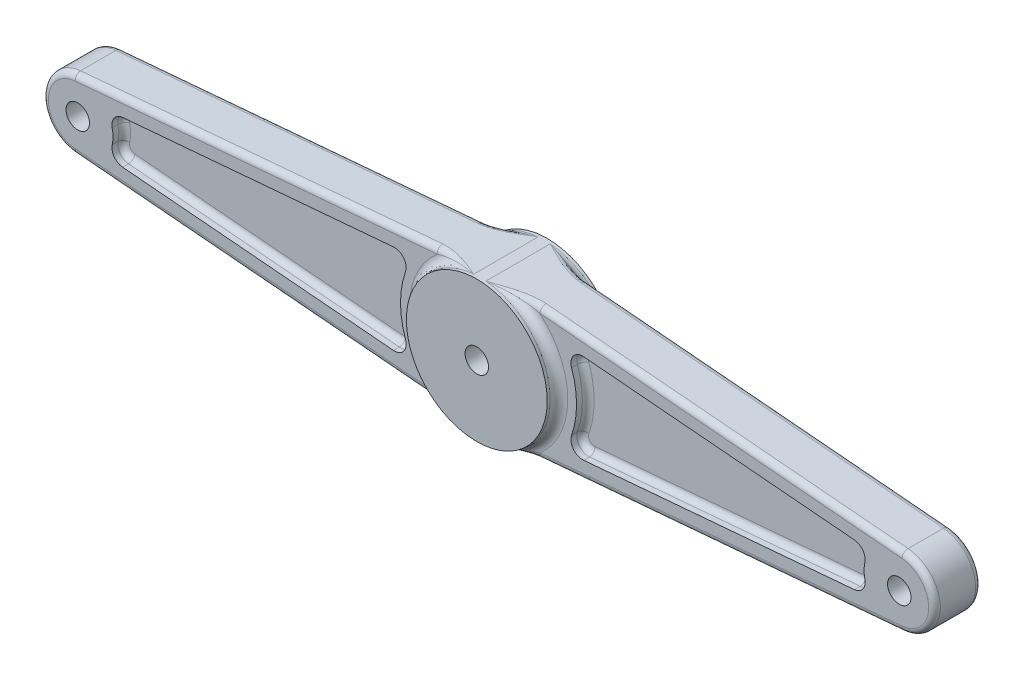
SolidWorks part; units mm, degrees
material "AISI 4340 Steel, annealed"
ref_plane "Front Plane" through (0, 0, 0) normal (0, 0, 1) x (1, 0, 0)
ref_plane "Top Plane" through (0, 0, 0) normal (0, 1, 0) x (1, 0, 0)
ref_plane "Right Plane" through (0, 0, 0) normal (1, 0, 0) x (0, 0, -1)
sketch "Sketch1" plane through (0, 0, 0) normal (0, 0, 1) x (1, 0, 0)
  line L0 (-70.5143, 5.9779) -> (-1.0286, 11.9558)
  line L1 (70.5143, 5.9779) -> (1.0286, 11.9558)
  line L2 (1.0286, -11.9558) -> (70.5143, -5.9779)
  line L3 (-70.5143, -5.9779) -> (-1.0286, -11.9558)
  arc A0 (-1.0286, -11.9558) -> (1.0286, -11.9558) centre (0, 0) ccw
  arc A1 (70.5143, -5.9779) -> (70.5143, 5.9779) centre (70, 0) ccw
  arc A2 (-70.5143, 5.9779) -> (-70.5143, -5.9779) centre (-70, 0) ccw
  arc A3 (1.0286, 11.9558) -> (-1.0286, 11.9558) centre (0, 0) ccw
  circle A4 centre (-70, 0) radius 2
  circle A5 centre (0, 0) radius 2
  circle A6 centre (70, 0) radius 2
  dimension "D1" = 24
  dimension "D2" = 12
  dimension "D3" = 140
  dimension "D5" = 4
  dimension "D4" = 70
extrude "Boss-Extrude1" add sketch "Sketch1" along normal mid plane 8
sketch "Sketch2" plane through (0, 0, 0) normal (0, 0, 1) x (1, 0, 0)
  circle A0 centre (0, 0) radius 12
  dimension "D1" = 24
extrude "Boss-Extrude2" add sketch "Sketch2" along normal mid plane 12
sketch "Sketch3" plane through (0, 0, 4) normal (0, 0, 1) x (1, 0, 0)
  circle A0 centre (0, 0) radius 2
  dimension "D1" = 4
extrude "Cut-Extrude1" cut sketch "Sketch3" against normal mid plane 45
sketch "Sketch4" plane through (0, 0, 4) normal (0, 0, 1) x (1, 0, 0)
  line L0 (16.2063, -7.639) -> (62.3491, -3.6693)
  line L1 (1.0286, -11.9558) -> (70.5143, -5.9779) construction
  line L6 (-62.3491, 3.6693) -> (-16.2063, 7.639)
  line L8 (-62.3491, -3.6693) -> (-16.2063, -7.639)
  line L9 (16.2063, 7.639) -> (62.3491, 3.6693)
  arc A0 (-14.1485, 4.9821) -> (-14.1485, -4.9821) centre (0, 0) ccw
  arc A1 (-64.1333, -1.2575) -> (-64.1333, 1.2575) centre (-70, 0) ccw
  arc A2 (1.0286, -11.9558) -> (1.0286, 11.9558) centre (0, 0) ccw construction
  arc A3 (64.1333, 1.2575) -> (64.1333, -1.2575) centre (70, 0) ccw
  arc A5 (14.1485, -4.9821) -> (14.1485, 4.9821) centre (0, 0) ccw
  arc A6 (64.1333, -1.2575) -> (62.3491, -3.6693) centre (62.1777, -1.6767) cw
  arc A7 (64.1333, 1.2575) -> (62.3491, 3.6693) centre (62.1777, 1.6767) ccw
  arc A8 (16.2063, -7.639) -> (14.1485, -4.9821) centre (16.0349, -5.6464) cw
  arc A9 (16.2063, 7.639) -> (14.1485, 4.9821) centre (16.0349, 5.6464) ccw
  arc A10 (-14.1485, -4.9821) -> (-16.2063, -7.639) centre (-16.0349, -5.6464) cw
  arc A11 (-14.1485, 4.9821) -> (-16.2063, 7.639) centre (-16.0349, 5.6464) ccw
  arc A12 (-62.3491, -3.6693) -> (-64.1333, -1.2575) centre (-62.1777, -1.6767) cw
  arc A13 (-62.3491, 3.6693) -> (-64.1333, 1.2575) centre (-62.1777, 1.6767) ccw
  point P20 (65.0801, 3.4343)
  point P26 (12.7273, 7.9383)
  point P30 (-12.7273, -7.9383)
  point P36 (-12.7273, 7.9383)
  point P39 (-65.0801, -3.4343)
  point P42 (-65.0801, 3.4343)
  dimension "D1" = 3
  dimension "D2" = 6
  dimension "D3" = 12
  dimension "D13" = 2
  dimension "D4" = 3
  dimension "D5" = 5.4342
  dimension "D6" = 57.787
  dimension "D7" = 83.2416
  dimension "D8" = 83.2416
  dimension "D9" = 69.4857
  dimension "D10" = 69.4857
  dimension "D11" = 135.5944
  dimension "D12" = 135.5944
extrude "Cut-Extrude2" cut sketch "Sketch4" against normal blind 2
mirror "Mirror1" about plane through (0, 0, 0) normal (0, 0, 1) of "Cut-Extrude2"
fillet "Fillet1" radius 1 16 edges at (-14.4537, 6.871, 2) (-15, 0, 2) (-14.4537, -6.871, 2) (-39.2777, -5.6541, 2) (-63.7855, -2.8661, 2) (-64, 0, 2) (-63.7855, 2.8661, 2) (14.4537, 6.871, 2) (39.2777, 5.6541, 2) (63.7855, 2.8661, 2) (64, 0, 2) (63.7855, -2.8661, 2) (39.2777, -5.6541, 2) (14.4537, -6.871, 2) (-39.2777, 5.6541, 2) (15, 0, 2)
fillet "Fillet2" radius 1 16 edges at (63.7855, 2.8661, -2) (64, 0, -2) (63.7855, -2.8661, -2) (39.2777, -5.6541, -2) (14.4537, -6.871, -2) (15, 0, -2) (14.4537, 6.871, -2) (-14.4537, -6.871, -2) (-39.2777, -5.6541, -2) (-63.7855, -2.8661, -2) (-64, 0, -2) (-63.7855, 2.8661, -2) (-39.2777, 5.6541, -2) (-14.4537, 6.871, -2) (39.2777, 5.6541, -2) (-15, 0, -2)
fillet "Fillet3" radius 1.5 4 edges at (12, 0, 4) (-12, 0, 4) (-12, 0, -4) (12, 0, -4)
fillet "Fillet4" radius 1 20 edges at (-4.2015, 11.6829, 4.4638) (-38.8524, 8.7018, 4) (-76, 0, 4) (-4.2015, -11.6829, 4.4638) (4.2015, -11.6829, 4.4638) (38.8524, -8.7018, 4) (76, 0, 4) (4.2015, 11.6829, 4.4638) (-4.2015, 11.6829, -4.4638) (-4.2015, -11.6829, -4.4638) (-38.8524, -8.7018, -4) (-76, 0, -4) (4.2015, -11.6829, -4.4638) (4.2015, 11.6829, -4.4638) (38.8524, 8.7018, -4) (76, 0, -4) (-38.8524, -8.7018, 4) (38.8524, 8.7018, 4) (-38.8524, 8.7018, -4) (38.8524, -8.7018, -4)
